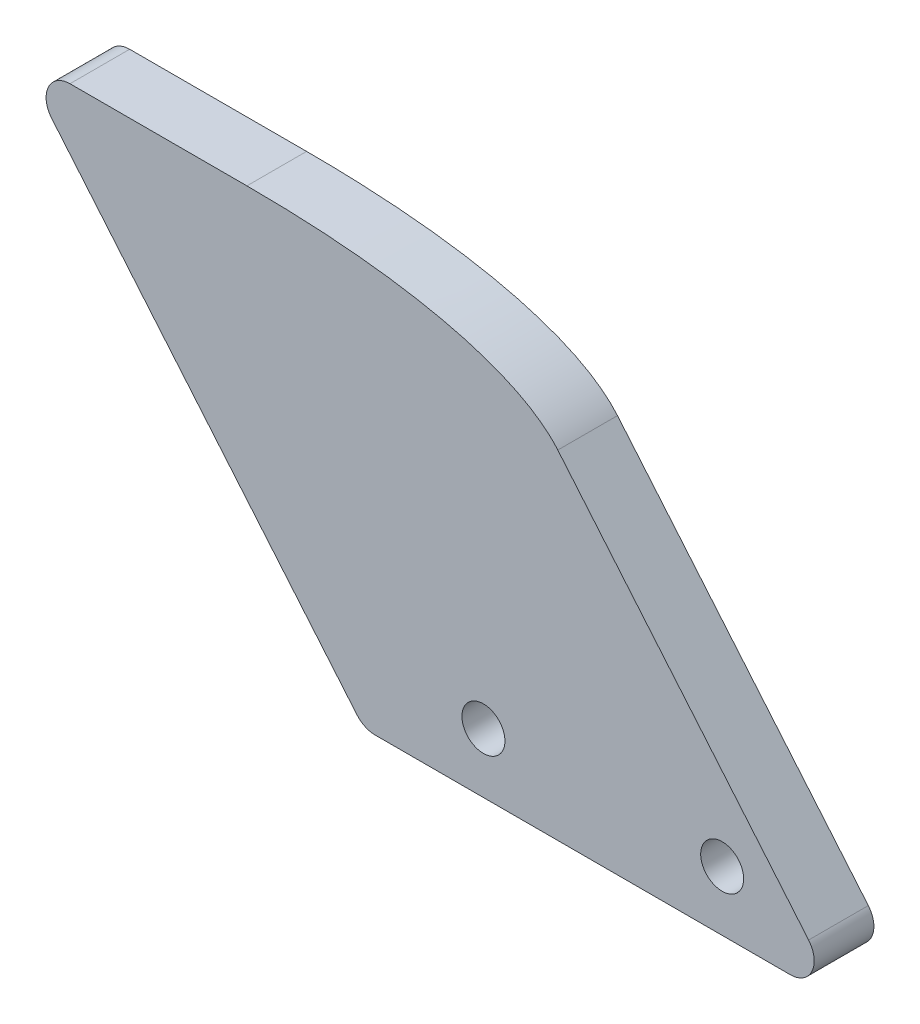
SolidWorks part; units mm, degrees
ref_plane "Front Plane" through (0, 0, 0) normal (0, 0, 1) x (1, 0, 0)
ref_plane "Top Plane" through (0, 0, 0) normal (0, 1, 0) x (1, 0, 0)
ref_plane "Right Plane" through (0, 0, 0) normal (1, 0, 0) x (0, 0, -1)
sketch "Sketch1" plane through (0, 0, 0) normal (0, 0, 1) x (1, 0, 0)
  line L0 (0, 0) -> (50.8, 0)
  line L2 (36.7353, -43.7794) -> (0, 0)
  line L3 (50.8, 0) -> (87.5353, -43.7794)
  line L4 (87.5353, -43.7794) -> (36.7353, -43.7794)
  point P4 (32.6536, -38.9151)
  dimension "D1" = 50.8
  dimension "D2" = 57.15
  dimension "D3" = 130
extrude "Boss-Extrude1" add sketch "Sketch1" along normal blind 6.35
sketch "Sketch2" plane through (0, 0, 6.35) normal (0, 0, 1) x (1, 0, 0)
  line L0 (36.7353, -43.7794) -> (87.5353, -43.7794) construction
  line L1 (87.5353, -43.7794) -> (87.5353, -21.9757) construction
  circle A0 centre (74.8353, -37.4294) radius 2.286
  circle A1 centre (49.4353, -37.4294) radius 2.286
  dimension "D1" = 4.572
  dimension "D2" = 12.7
  dimension "D3" = 6.35
  dimension "D4" = 2
extrude "Cut-Extrude1" cut sketch "Sketch2" against normal through all contours A1 | A0
fillet "Fillet1" radius 35.56 1 edges at (50.8, 0, 3.175) second distance 43.18 first distance on face at (69.1677, -21.8897, 3.175)
fillet "Fillet2" radius 2.54 3 edges at (87.5353, -43.7794, 3.175) (0, 0, 3.175) (36.7353, -43.7794, 3.175)
